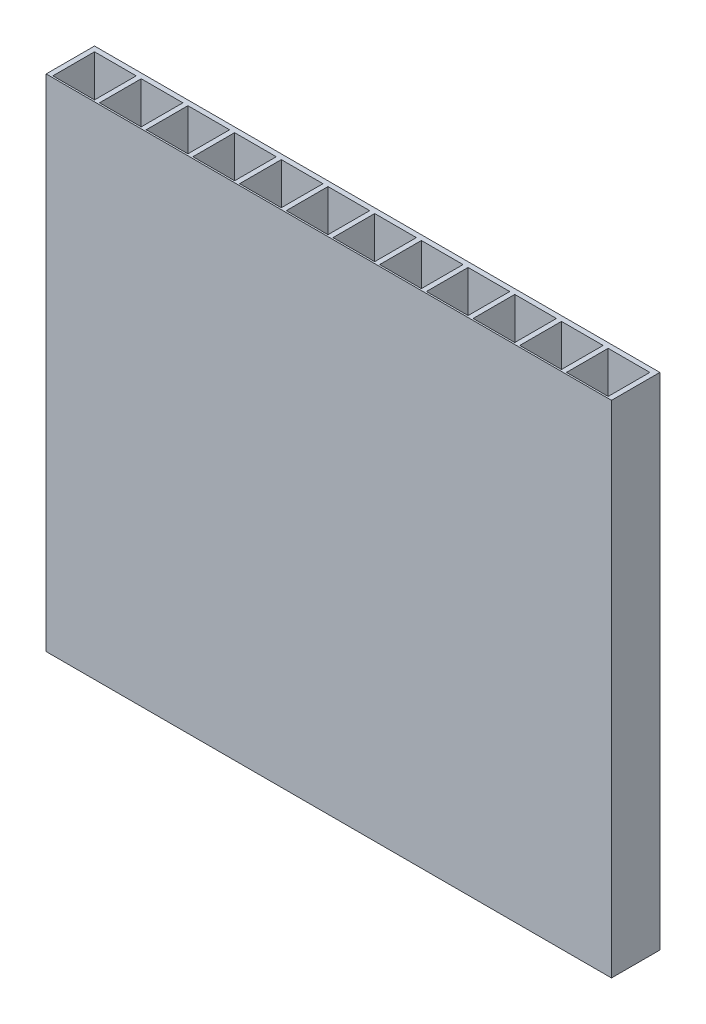
SolidWorks part; units mm, degrees
ref_plane "Front Plane" through (0, 0, 0) normal (0, 0, 1) x (1, 0, 0)
ref_plane "Top Plane" through (0, 0, 0) normal (0, 1, 0) x (1, 0, 0)
ref_plane "Right Plane" through (0, 0, 0) normal (1, 0, 0) x (0, 0, -1)
sketch "Sketch1" plane through (0, 0, 0) normal (0, 1, 0) x (1, 0, 0)
  line L1 (-3.175, -3.175) -> (3.175, -3.175)
  line L2 (-3.175, -3.175) -> (-3.175, 3.175)
  line L3 (-3.175, 3.175) -> (3.175, 3.175)
  line L4 (3.175, -3.175) -> (3.175, 3.175)
  line L5 (-3.175, -3.175) -> (3.175, 3.175) construction
  line L6 (-3.175, 3.175) -> (3.175, -3.175) construction
  line L7 (-3.937, -3.937) -> (3.937, -3.937)
  line L8 (-3.937, -3.937) -> (-3.937, 3.937)
  line L9 (-3.937, 3.937) -> (3.937, 3.937)
  line L10 (3.937, -3.937) -> (3.937, 3.937)
  line L11 (-3.937, -3.937) -> (3.937, 3.937) construction
  line L12 (-3.937, 3.937) -> (3.937, -3.937) construction
  point P0 (0, 0)
  point P6 (0, 0)
  dimension "D1" = 0.762
  dimension "D2" = 6.35
extrude "Boss-Extrude1" add sketch "Sketch1" along normal blind 76.2
pattern_linear "LPattern1" count 12 spacing 7.112 along (1, 0, 0) of "Boss-Extrude1"
sketch "Sketch3" plane through (0, 0, 0) normal (0, 0, 1) x (1, 0, 0)
  line L4 (82.169, 0) -> (82.169, 76.2)
  line L5 (82.169, 76.2) -> (-3.937, 76.2)
  line L6 (-3.937, 76.2) -> (-3.937, 0)
  line L7 (-3.937, 0) -> (82.169, 0)
  line L8 (82.169, 0) -> (82.169, 76.2)
  line L9 (82.169, 76.2) -> (-3.937, 76.2)
  line L10 (-3.937, 76.2) -> (-3.937, 0)
  line L11 (-3.937, 0) -> (82.169, 0)
  dimension "D1" = 0
extrude "Cut-Extrude1" cut sketch "Sketch3" against normal blind 0.508 from surface starting at face at (39.116, 38.1, 3.937)
equation "\"column_diameter\"=0.25"
equation "\"D2@Sketch1\"=\"column_diameter\""
equation "\"wall_thickness\"= 0.03"
equation "\"D1@Sketch1\"=\"wall_thickness\""
equation "\"D3@LPattern1\"=\"column_diameter\"+\"wall_thickness\""
